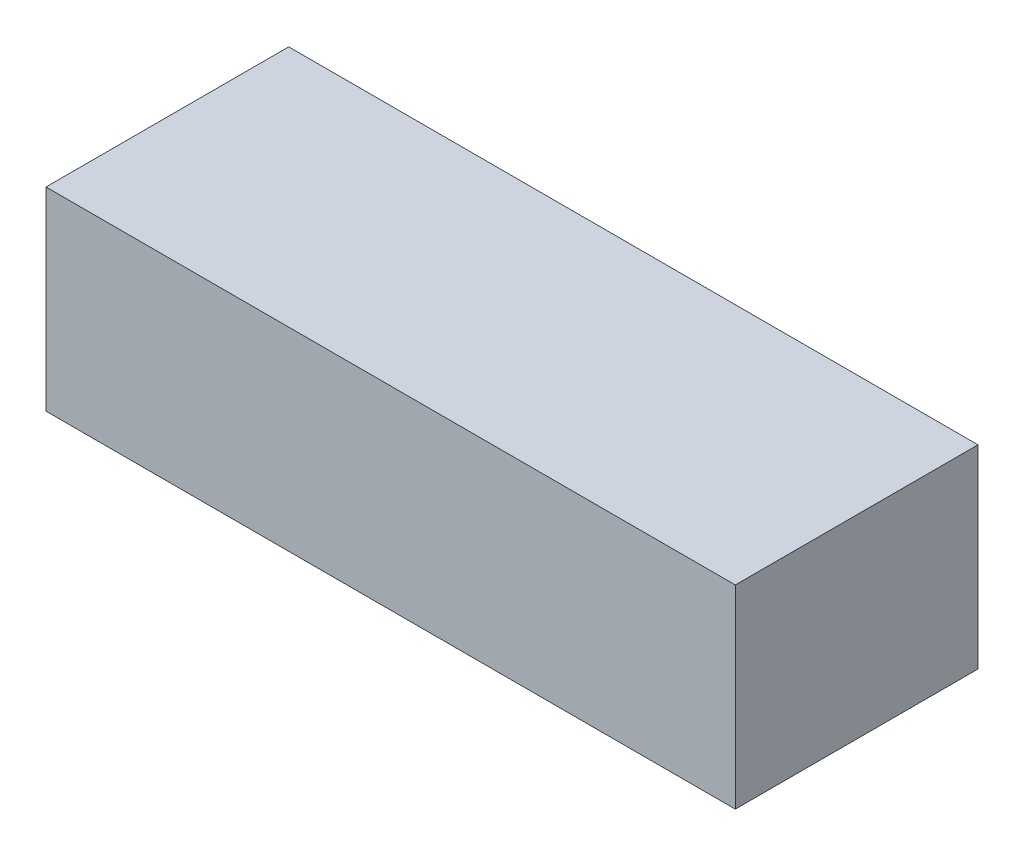
SolidWorks part; units mm, degrees
ref_plane "Front Plane" through (0, 0, 0) normal (0, 0, 1) x (1, 0, 0)
ref_plane "Top Plane" through (0, 0, 0) normal (0, 1, 0) x (1, 0, 0)
ref_plane "Right Plane" through (0, 0, 0) normal (1, 0, 0) x (0, 0, -1)
sketch "Sketch1" plane through (0, 0, 0) normal (0, 1, 0) x (1, 0, 0)
  line L1 (-17.75, -6.25) -> (17.75, -6.25)
  line L2 (-17.75, -6.25) -> (-17.75, 6.25)
  line L3 (-17.75, 6.25) -> (17.75, 6.25)
  line L4 (17.75, -6.25) -> (17.75, 6.25)
  line L5 (-17.75, -6.25) -> (17.75, 6.25) construction
  line L6 (-17.75, 6.25) -> (17.75, -6.25) construction
  point P0 (0, 0)
  dimension "D1" = 12.5
  dimension "D2" = 35.5
extrude "Boss-Extrude1" add sketch "Sketch1" along normal blind 10
sketch "Sketch2" plane through (0, 0, 0) normal (0, -1, 0) x (1, 0, 0)
  line L0 (-17.75, -6.25) -> (-17.75, 6.25) construction
  line L2 (-12.75, 1.25) -> (-12.75, -6.25)
  line L3 (17.75, -6.25) -> (-17.75, -6.25) construction
  line L4 (0, 6.25) -> (0, -6.25) construction
  line L5 (-17.75, 6.25) -> (17.75, 6.25) construction
  line L6 (12.75, 1.25) -> (12.75, -6.25)
  line L7 (-12.75, 1.25) -> (12.75, 1.25)
  line L8 (-12.75, -6.25) -> (12.75, -6.25)
  dimension "D1" = 7.5
  dimension "D2" = 5
extrude "Cut-Extrude1" cut sketch "Sketch2" against normal blind 7.5
sketch "Sketch4" plane through (0, 0, -6.25) normal (0, 0, -1) x (-1, 0, 0)
  line L0 (0, 0) -> (0, 10) construction
  line L1 (-17.75, 10) -> (17.75, 10) construction
  line L2 (-17.75, 10) -> (-17.75, 0) construction
  line L3 (-17.75, 0) -> (-12.75, 0) construction
  circle A0 centre (-14.75, 3) radius 1
  circle A1 centre (14.75, 3) radius 1
  dimension "D1" = 3
  dimension "D2" = 2
  dimension "D3" = 3
extrude "Cut-Extrude2" cut sketch "Sketch4" against normal blind 4
